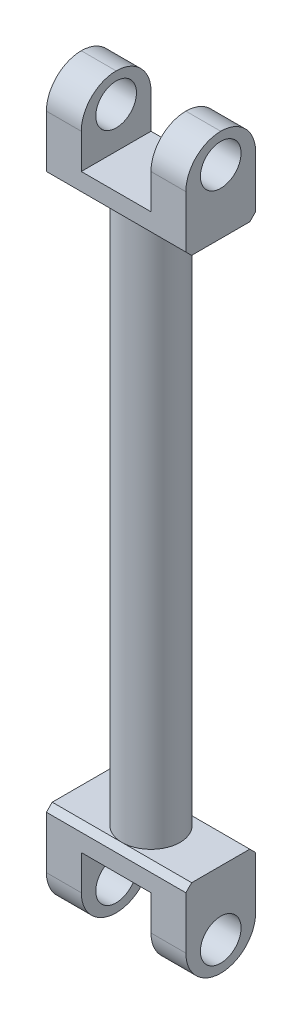
SolidWorks part; units mm, degrees
material "PLA"
ref_plane "Front Plane" through (0, 0, 0) normal (0, 0, 1) x (1, 0, 0)
ref_plane "Top Plane" through (0, 0, 0) normal (0, 1, 0) x (1, 0, 0)
ref_plane "Right Plane" through (0, 0, 0) normal (1, 0, 0) x (0, 0, -1)
sketch "Sketch1" plane through (0, 0, 0) normal (0, 1, 0) x (1, 0, 0)
  circle A0 centre (0, 0) radius 2.5
  dimension "D1" = 5
extrude "Boss-Extrude1" add sketch "Sketch1" along normal mid plane 46.75
sketch "Sketch2" plane through (0, 23.375, 0) normal (0, 1, 0) x (1, 0, 0)
  line L1 (-6, -3) -> (6, -3)
  line L2 (-6, -3) -> (-6, 3)
  line L3 (-6, 3) -> (6, 3)
  line L4 (6, -3) -> (6, 3)
  line L5 (-6, -3) -> (6, 3) construction
  line L6 (-6, 3) -> (6, -3) construction
  point P0 (0, 0)
  dimension "D1" = 6
  dimension "D2" = 12
extrude "Boss-Extrude2" add sketch "Sketch2" along normal blind 2
sketch "Sketch3" plane through (0, 25.375, 0) normal (0, 1, 0) x (1, 0, 0)
  line L0 (-6, -3) -> (6, -3) construction
  line L1 (-6, 3) -> (-3, 3)
  line L2 (-6, 3) -> (-6, -3)
  line L3 (-6, -3) -> (-3, -3)
  line L4 (-3, 3) -> (-3, -3)
  line L6 (6, 3) -> (3, 3)
  line L7 (6, 3) -> (6, -3)
  line L8 (6, -3) -> (3, -3)
  line L9 (3, 3) -> (3, -3)
  dimension "D1" = 3
  dimension "D2" = 3
extrude "Boss-Extrude3" add sketch "Sketch3" along normal blind 6
sketch "Sketch4" plane through (-6, 0, 0) normal (-1, 0, 0) x (0, 0, 1)
  line L0 (0, -1000) -> (0, 49000) construction
  line L1 (-3, 31.375) -> (3, 31.375) construction
  circle A0 centre (0, 28.875) radius 1.75
  dimension "D1" = 3.5
  dimension "D2" = 2.5
extrude "Cut-Extrude1" cut sketch "Sketch4" against normal through all
fillet "Fillet1" radius 3 4 edges at (4.5, 31.375, 3) (4.5, 31.375, -3) (-4.5, 31.375, 3) (-4.5, 31.375, -3)
chamfer "Chamfer2" distance 0.5 angle 45 2 edges at (0, 23.375, -3) (0, 23.375, 3)
mirror "Mirror1" about plane through (0, 0, 0) normal (0, 1, 0) of "Boss-Extrude3", "Chamfer2", "Cut-Extrude1", "Fillet1", "Boss-Extrude2"
